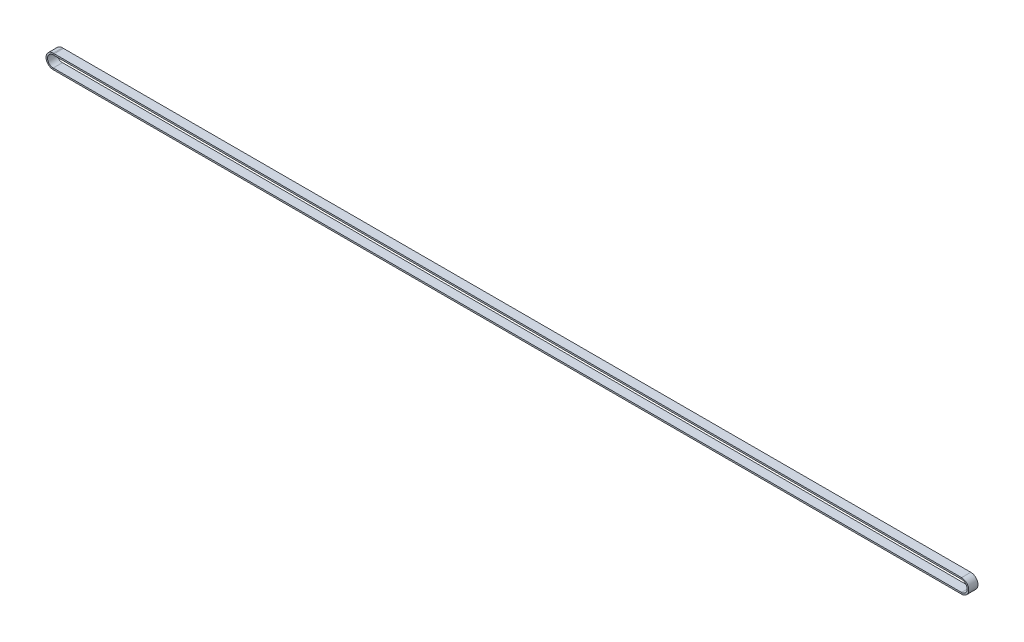
SolidWorks part; units mm, degrees
ref_plane "Front Plane" through (0, 0, 0) normal (0, 0, 1) x (1, 0, 0)
ref_plane "Top Plane" through (0, 0, 0) normal (0, 1, 0) x (1, 0, 0)
ref_plane "Right Plane" through (0, 0, 0) normal (1, 0, 0) x (0, 0, -1)
sketch "Sketch2" plane through (0, 0, 0) normal (0, 0, 1) x (1, 0, 0)
  line L0 (0, 0) -> (1, 0) construction
  line L1 (0, 0) -> (0, 1) construction
  line L2 (-1, -154.4016) -> (883.5203, -154.4016)
  line L3 (883.5203, -168.4016) -> (-1, -168.4016)
  arc A0 (-1, -168.4016) -> (-1, -154.4016) centre (-1, -161.4016) cw
  arc A1 (883.5203, -154.4016) -> (883.5203, -168.4016) centre (883.5203, -161.4016) cw
sketch "Sketch3" plane through (0, 0, 0) normal (1, 0, 0) x (0, 0, -1)
  line L1 (0, -155.9016) -> (-9, -155.9016)
  line L2 (0, -155.9016) -> (0, -154.4016)
  line L3 (0, -154.4016) -> (-9, -154.4016)
  line L4 (-9, -155.9016) -> (-9, -154.4016)
  dimension "D1" = 9
  dimension "D2" = 1.5
sweep "Sweep1" add profiles "Sketch3" path "Sketch2"
